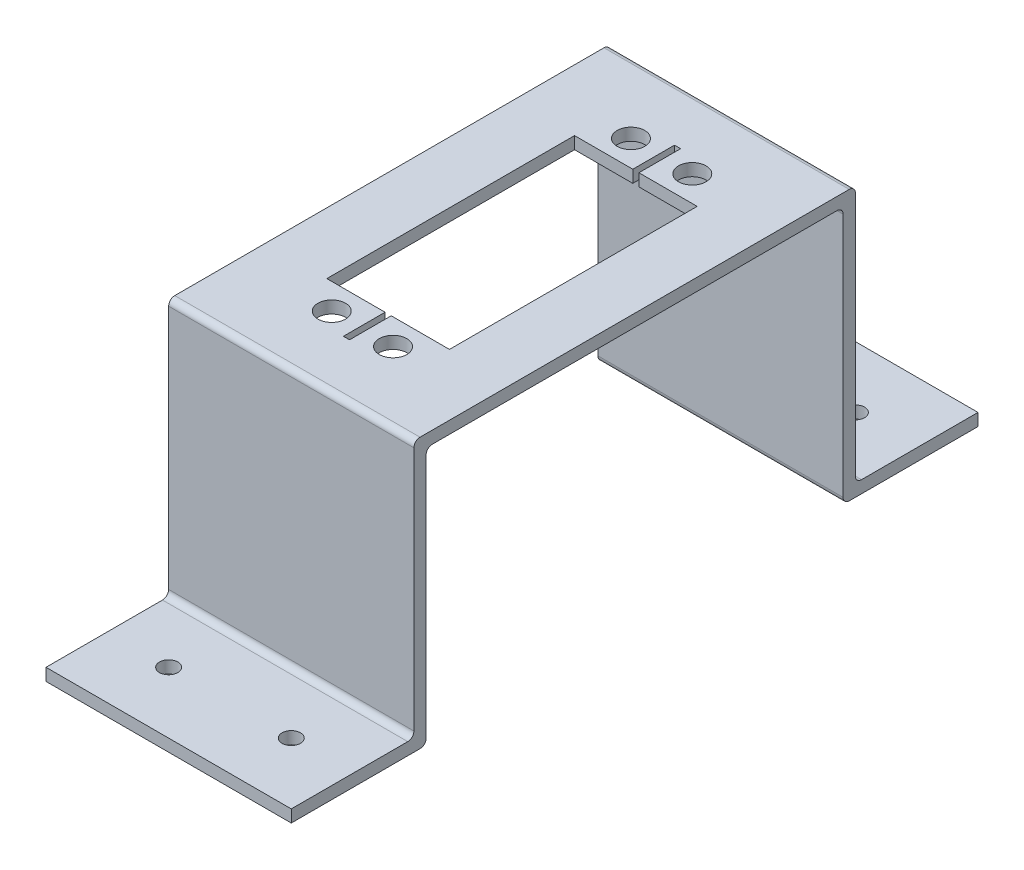
SolidWorks part; units mm, degrees
ref_plane "Front Plane" through (0, 0, 0) normal (0, 0, 1) x (1, 0, 0)
ref_plane "Top Plane" through (0, 0, 0) normal (0, 1, 0) x (1, 0, 0)
ref_plane "Right Plane" through (0, 0, 0) normal (1, 0, 0) x (0, 0, -1)
sketch "Sketch1" plane through (0, 0, 0) normal (0, 1, 0) x (1, 0, 0)
  line L0 (0.736, 26.632) -> (1.236, 26.632)
  line L1 (0.736, 26.632) -> (0.736, 19.832)
  line L2 (0.736, 19.832) -> (1.236, 19.832)
  line L3 (1.236, 26.632) -> (1.236, 19.832)
  line L4 (0.736, 26.632) -> (0.236, 26.632)
  line L5 (0.736, 26.632) -> (0.736, 19.832)
  line L6 (0.736, 19.832) -> (0.236, 19.832)
  line L7 (0.236, 26.632) -> (0.236, 19.832)
  line L8 (0.736, 19.832) -> (10.736, 19.832)
  line L9 (0.736, 19.832) -> (0.736, -20.568)
  line L10 (0.736, -20.568) -> (10.736, -20.568)
  line L11 (10.736, 19.832) -> (10.736, -20.568)
  line L12 (0.736, 19.832) -> (-9.264, 19.832)
  line L13 (0.736, 19.832) -> (0.736, -20.568)
  line L14 (0.736, -20.568) -> (-9.264, -20.568)
  line L15 (-9.264, 19.832) -> (-9.264, -20.568)
  line L16 (0.736, -20.568) -> (1.236, -20.568)
  line L17 (0.736, -20.568) -> (0.736, -27.368)
  line L18 (0.736, -27.368) -> (1.236, -27.368)
  line L19 (1.236, -20.568) -> (1.236, -27.368)
  line L20 (0.736, -20.568) -> (0.236, -20.568)
  line L21 (0.736, -20.568) -> (0.736, -27.368)
  line L22 (0.736, -27.368) -> (0.236, -27.368)
  line L23 (0.236, -20.568) -> (0.236, -27.368)
  line L25 (-19.264, 49.632) -> (20.736, 49.632)
  line L26 (-19.264, 49.632) -> (-19.264, -50.368)
  line L27 (-19.264, -50.368) -> (20.736, -50.368)
  line L28 (20.736, 49.632) -> (20.736, -50.368)
  circle A0 centre (-4.264, 24.032) radius 2.25
  circle A1 centre (5.736, 24.032) radius 2.25
  circle A2 centre (5.736, -24.768) radius 2.25
  circle A3 centre (-4.264, -24.768) radius 2.25
  circle A4 centre (-9.264, 39.632) radius 1.5
  circle A5 centre (10.736, 39.632) radius 1.5
  circle A6 centre (10.736, -40.368) radius 1.5
  circle A7 centre (-9.264, -40.368) radius 1.5
  dimension "D24" = 10
  dimension "D26" = 10
  dimension "D27" = 10
  dimension "D28" = 10
  dimension "D29" = 10
  dimension "D30" = 10
  dimension "D31" = 10
  dimension "D1" = 0.5
  dimension "D2" = 0.5
  dimension "D3" = 6.8
  dimension "D4" = 40.4
  dimension "D5" = 10
  dimension "D6" = 10
  dimension "D7" = 4.5
  dimension "D8" = 4.2
  dimension "D9" = 4.5
  dimension "D10" = 4.2
  dimension "D11" = 0.5
  dimension "D12" = 0.5
  dimension "D13" = 6.8
  dimension "D14" = 4.2
  dimension "D15" = 4.5
  dimension "D16" = 4.5
  dimension "D17" = 4.2
  dimension "D18" = 100
  dimension "D19" = 40
  dimension "D20" = 23
  dimension "D21" = 23
  dimension "D22" = 10
  dimension "D23" = 10
  dimension "D25" = 10
extrude "Boss-Extrude1" add sketch "Sketch1" along normal blind 2 contours L28 L25 L26 L27 A7 A6 A5 A4 A3 A2 A1 A0 L23 L14 L15 L12 L7 L4 L0 L3 L8 L11 L10 L19 L18 L22 region at (0.736, 0, -48.555)
sketch "Sketch2" plane through (0, 2, 0) normal (0, 1, 0) x (1, 0, 0)
  line L0 (20.736, 49.632) -> (20.736, -50.368) construction
  line L1 (-19.264, 49.632) -> (20.736, 49.632)
  line L2 (-19.264, 49.632) -> (-19.264, 33.632)
  line L3 (-19.264, 33.632) -> (20.736, 33.632)
  line L4 (20.736, 49.632) -> (20.736, 33.632)
  line L6 (-19.264, -50.368) -> (20.736, -50.368)
  line L7 (-19.264, -50.368) -> (-19.264, -34.368)
  line L8 (-19.264, -34.368) -> (20.736, -34.368)
  line L9 (20.736, -50.368) -> (20.736, -34.368)
  dimension "D1" = 40
  dimension "D2" = 16
  dimension "D3" = 40
  dimension "D4" = 16
extrude "Cut-Extrude1" cut sketch "Sketch2" against normal blind 10
sketch "Sketch4" plane through (0, 2, 0) normal (0, 1, 0) x (1, 0, 0)
  line L1 (-19.264, -34.368) -> (20.736, -34.368)
  line L2 (-19.264, -34.368) -> (-19.264, -36.368)
  line L3 (-19.264, -36.368) -> (20.736, -36.368)
  line L4 (20.736, -34.368) -> (20.736, -36.368)
  line L5 (20.736, 33.632) -> (-19.264, 33.632)
  line L6 (20.736, 33.632) -> (20.736, 35.632)
  line L7 (20.736, 35.632) -> (-19.264, 35.632)
  line L8 (-19.264, 33.632) -> (-19.264, 35.632)
  dimension "D1" = 2
  dimension "D2" = 40
  dimension "D3" = 40
  dimension "D4" = 2
extrude "Boss-Extrude2" add sketch "Sketch4" against normal blind 44
sketch "Sketch5" plane through (0, 0, -35.632) normal (0, 0, -1) x (-1, 0, 0)
  line L0 (19.264, -42) -> (19.264, 2) construction
  line L1 (-20.736, -42) -> (19.264, -42)
  line L2 (-20.736, -42) -> (-20.736, -40)
  line L3 (-20.736, -40) -> (19.264, -40)
  line L4 (19.264, -42) -> (19.264, -40)
  dimension "D1" = 2
  dimension "D2" = 40
extrude "Boss-Extrude3" add sketch "Sketch5" along normal blind 20
sketch "Sketch6" plane through (0, 0, 36.368) normal (0, 0, 1) x (1, 0, 0)
  line L0 (20.736, -42) -> (20.736, 2) construction
  line L1 (-19.264, -42) -> (20.736, -42)
  line L2 (-19.264, -42) -> (-19.264, -40)
  line L3 (-19.264, -40) -> (20.736, -40)
  line L4 (20.736, -42) -> (20.736, -40)
  dimension "D1" = 40
  dimension "D2" = 2
extrude "Boss-Extrude4" add sketch "Sketch6" along normal blind 20
fillet "Fillet1" radius 1 8 edges at (0.736, -42, -33.632) (0.736, -40, -35.632) (0.736, 2, -35.632) (0.736, 0, -33.632) (0.736, 0, 34.368) (0.736, 2, 36.368) (0.736, -42, 34.368) (0.736, -40, 36.368)
sketch "Sketch7" plane through (0, -40, 0) normal (0, 1, 0) x (1, 0, 0)
  line L0 (20.736, 55.632) -> (20.736, 36.632) construction
  line L1 (-19.264, 55.632) -> (20.736, 55.632) construction
  line L2 (-19.264, 55.632) -> (-19.264, 36.632) construction
  circle A0 centre (-9.264, 45.632) radius 1.5
  circle A1 centre (10.736, 45.632) radius 1.5
  dimension "D1" = 3
  dimension "D2" = 3
  dimension "D3" = 10
  dimension "D4" = 10
  dimension "D5" = 10
  dimension "D6" = 10
extrude "Cut-Extrude2" cut sketch "Sketch7" against normal blind 20
sketch "Sketch8" plane through (0, -40, 0) normal (0, 1, 0) x (1, 0, 0)
  line L0 (20.736, -56.368) -> (20.736, -37.368) construction
  line L1 (20.736, -56.368) -> (-19.264, -56.368) construction
  line L2 (-19.264, -56.368) -> (-19.264, -37.368) construction
  circle A0 centre (10.736, -46.368) radius 1.5
  circle A1 centre (-9.264, -46.368) radius 1.5
  dimension "D1" = 10
  dimension "D2" = 10
  dimension "D3" = 10
  dimension "D4" = 10
extrude "Cut-Extrude3" cut sketch "Sketch8" against normal blind 20
